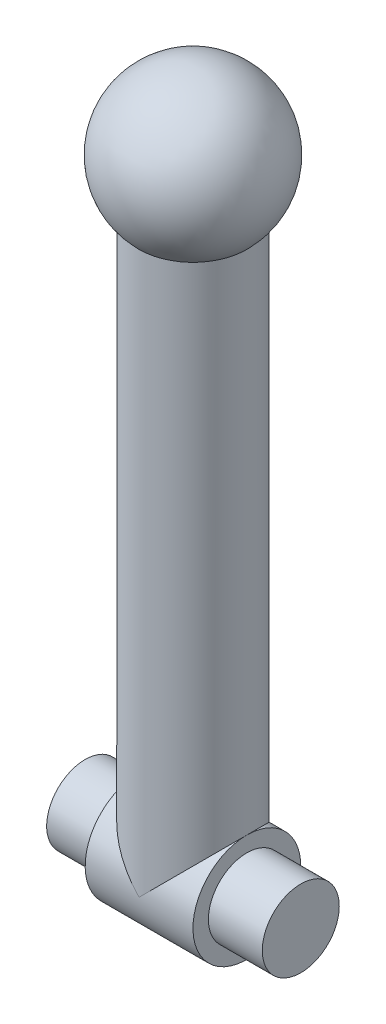
SolidWorks part; units mm, degrees
ref_plane "Front Plane" through (0, 0, 0) normal (0, 0, 1) x (1, 0, 0)
ref_plane "Top Plane" through (0, 0, 0) normal (0, 1, 0) x (1, 0, 0)
ref_plane "Right Plane" through (0, 0, 0) normal (1, 0, 0) x (0, 0, -1)
sketch "Sketch1" plane through (0, 0, 0) normal (0, 1, 0) x (1, 0, 0)
  circle A0 centre (0, 0) radius 35
extrude "Boss-Extrude1" add sketch "Sketch1" along normal blind 400
sketch "Sketch2" plane through (0, 400, 0) normal (0, 1, 0) x (1, 0, 0)
  line L0 (0, 50) -> (0, -50)
  arc A0 (0, -50) -> (0, 50) centre (0, 0) ccw
revolve "Revolve1" add sketch "Sketch2" angle 360 about L0 region at (14.8545, 400, 0)
sketch "Sketch3" plane through (0, 0, 0) normal (1, 0, 0) x (0, 0, -1)
  circle A0 centre (0, 0) radius 35
extrude "Boss-Extrude2" add sketch "Sketch3" along normal blind 35 and the other way blind 35
sketch "Sketch4" plane through (35, 0, 0) normal (1, 0, 0) x (0, 0, -1)
  circle A0 centre (0, 0) radius 25
extrude "Boss-Extrude3" add sketch "Sketch4" along normal blind 35
mirror "Mirror1" about plane through (0, 0, 0) normal (1, 0, 0) of "Boss-Extrude3"
